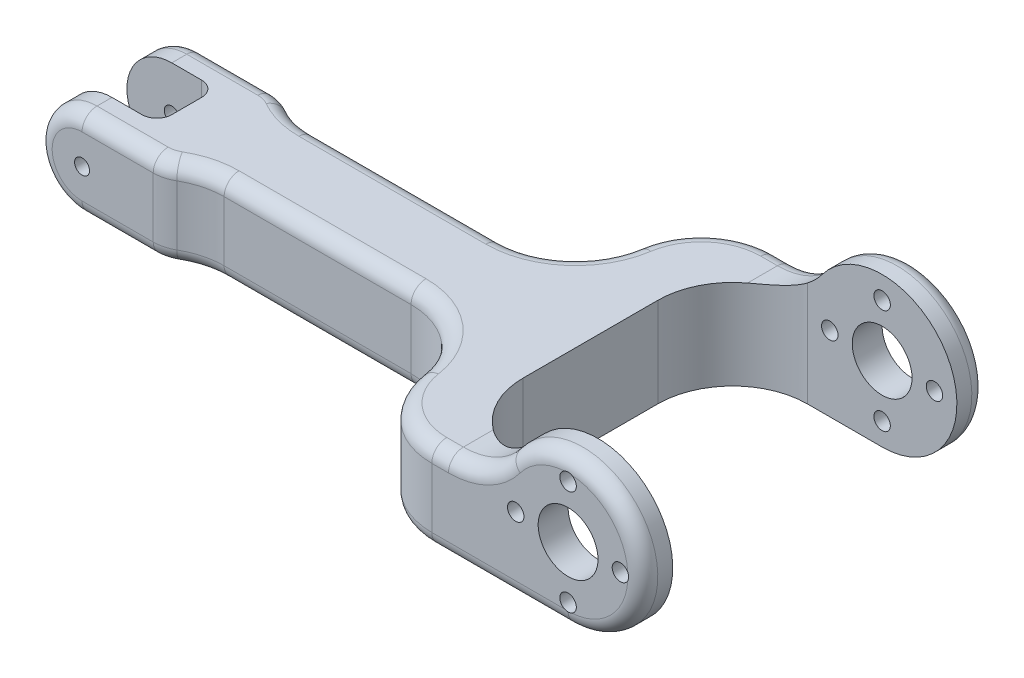
SolidWorks part; units mm, degrees
material "ABS"
ref_plane "Front Plane" through (0, 0, 0) normal (0, 0, 1) x (1, 0, 0)
ref_plane "Top Plane" through (0, 0, 0) normal (0, 1, 0) x (1, 0, 0)
ref_plane "Right Plane" through (0, 0, 0) normal (1, 0, 0) x (0, 0, -1)
sketch "Sketch1" plane through (0, 0, 0) normal (0, 0, 1) x (1, 0, 0)
  line L1 (-40, 6) -> (40, 6)
  line L2 (-40, 6) -> (-40, -6)
  line L3 (-40, -6) -> (40, -6)
  line L4 (40, 6) -> (40, -6)
  line L5 (-40, 6) -> (40, -6) construction
  line L6 (-40, -6) -> (40, 6) construction
  circle A0 centre (40, 4) radius 10
  circle A1 centre (40, 4) radius 4
  circle A2 centre (-40, 0) radius 6
  circle A3 centre (-40, 0) radius 1
  circle A4 centre (40, 11) radius 1.1
  circle A5 centre (47, 4) radius 1.1
  circle A6 centre (40, -3) radius 1.1
  circle A7 centre (33, 4) radius 1.1
  point P0 (0, 0)
  point P23 (40, 4)
  dimension "D1" = 20
  dimension "D2" = 8
  dimension "D5" = 40
  dimension "D6" = 2
  dimension "D7" = 2.2
  dimension "D8" = 7
  dimension "D10" = 7
  dimension "D3" = 80
  dimension "D4" = 12
  dimension "D9" = 4
extrude "Boss-Extrude2" add sketch "Sketch1" along normal blind 23 and the other way blind 23 contours A2 L3 A0 L1 | A3 L2 A2 | A3 L2 A2 | A7 L1 A0 L4 A6 A1 | A7 L1 A1 L4 A6 A0 A5 A4 region at (-37.3929, 0, 0) region at (-1.722, -0.0995, 0) region at (-42.6071, 0, 0) region at (40.9768, 13.6694, 0) region at (34.9161, 0.0492, 0)
sketch "Sketch2" plane through (0, 0, 0) normal (0, 1, 0) x (1, 0, 0)
  line L0 (-46, 23) -> (-46, -23) construction
  line L1 (-46, 4) -> (-34, 4)
  line L2 (-46, 4) -> (-46, -4)
  line L3 (-46, -4) -> (-34, -4)
  line L4 (-34, 4) -> (-34, -4)
  line L5 (50, -23) -> (50, 23) construction
  line L7 (50, 19) -> (20, 19)
  line L8 (50, 19) -> (50, -19)
  line L9 (50, -19) -> (20, -19)
  line L10 (20, 19) -> (20, -19)
  line L11 (-46, 23) -> (12, 23)
  line L12 (-46, 23) -> (-46, 8)
  line L13 (-46, 8) -> (12, 8)
  line L14 (12, 23) -> (12, 8)
  line L15 (-46, -23) -> (12, -23)
  line L16 (-46, -23) -> (-46, -8)
  line L17 (-46, -8) -> (12, -8)
  line L18 (12, -23) -> (12, -8)
  line L19 (-29, 8) -> (12, 8)
  line L20 (-29, 8) -> (-29, 6)
  line L21 (-29, 6) -> (12, 6)
  line L22 (12, 8) -> (12, 6)
  line L23 (-29, -8) -> (12, -8)
  line L24 (-29, -8) -> (-29, -6)
  line L25 (-29, -6) -> (12, -6)
  line L26 (12, -8) -> (12, -6)
  dimension "D1" = 8
  dimension "D2" = 4
  dimension "D3" = 12
  dimension "D4" = 38
  dimension "D5" = 19
  dimension "D6" = 30
  dimension "D7" = 8
  dimension "D8" = 8
  dimension "D9" = 4
  dimension "D10" = 4
  dimension "D11" = 5
  dimension "D12" = 5
  dimension "D13" = 6
  dimension "D14" = 6
extrude "Cut-Extrude1" cut sketch "Sketch2" against normal blind 23 and the other way blind 23 contours L14 L11 L12 L13 | L15 L18 L17 L16 | L4 L1 L2 L3 | L17 L26 L25 L24 | L22 L13 L20 L21 | L7 L10 L9 L8 region at (-40, 0, 0) region at (35, 0, 0) region at (-17, 0, -15.5) region at (-8.5, 0, -7) region at (-17, 0, 15.5) region at (-8.5, 0, 7)
fillet "Fillet1" radius 10 6 edges at (-29, 0, -6) (-29, 0, 6) (12, 0, -6) (12, 0, 6) (30.202, 6, 21) (30.202, 6, -21)
fillet "Fillet2" radius 10 4 edges at (12, 0, 23) (12, 0, -23) (20, 0, 19) (20, 0, -19)
fillet "Fillet3" radius 5 2 edges at (-29, 0, -8) (-29, 0, 8)
fillet "Fillet5" radius 2 34 edges at (-25.582, 6, 6.3391) (-29.1923, 6, 7.8305) (-35.2417, 6, 8) (-46, 0, 8) (-35.2417, -6, 8) (-29.1923, -6, 7.8305) (-25.582, -6, 6.3391) (-10.5, -6, 6) (8.5192, -6, 8.4171) (15.2545, -6, 20.5829) (30.8869, -6, 23) (48.9443, 8.4721, 23) (28.4721, 7.0557, 23) (22.8869, 6, 23) (15.2545, 6, 20.5829) (8.5192, 6, 8.4171) (-10.5, 6, 6) (-25.582, 6, -6.3391) (-29.1923, 6, -7.8305) (-35.2417, 6, -8) (-46, 0, -8) (-35.2417, -6, -8) (-29.1923, -6, -7.8305) (-25.582, -6, -6.3391) (-10.5, -6, -6) (8.5192, -6, -8.4171) (15.2545, -6, -20.5829) (30.8869, -6, -23) (48.9443, 8.4721, -23) (28.4721, 7.0557, -23) (22.8869, 6, -23) (15.2545, 6, -20.5829) (8.5192, 6, -8.4171) (-10.5, 6, -6)
fillet "Fillet6" radius 2 2 edges at (-34, 0, 4) (-34, 0, -4)
ref_axis "Axis1" through (40, 4, -23) along (0, 0, 1)
ref_point "Point1"
ref_axis "Axis2" through (40, 4, 0) along (-1, 0, 0)
